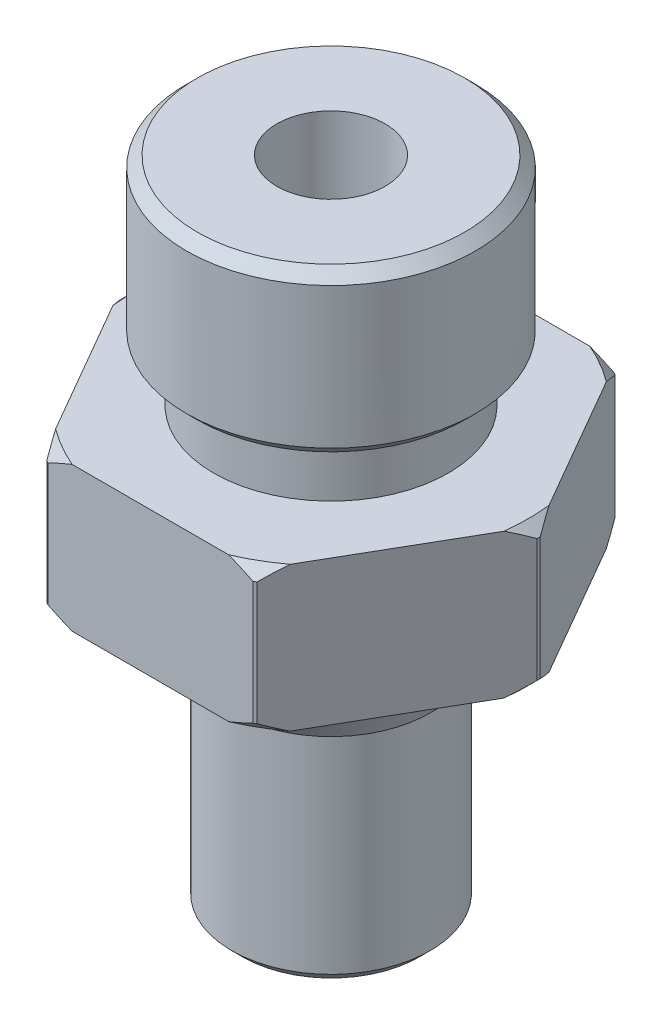
SolidWorks part; units mm, degrees
material "AISI 304"
ref_plane "Спереди" through (0, 0, 0) normal (0, 0, 1) x (1, 0, 0)
ref_plane "Сверху" through (0, 0, 0) normal (0, 1, 0) x (1, 0, 0)
ref_plane "Справа" through (0, 0, 0) normal (1, 0, 0) x (0, 0, -1)
ref_axis "ОсьX" through (-88.99, 0, 0) along (1, 0, 0)
ref_axis "ОсьZ" through (0, 55, 0) along (0, -1, 0)
ref_axis "ОсьY" through (0, 0, -88.99) along (0, 0, 1)
sketch "Эскиз1" plane through (0, 0, 0) normal (0, 0, 1) x (1, 0, 0)
  line L0 (0, 8.2669) -> (0, -10.3174) construction
  line L1 (1.5, 0) -> (4, 0)
  line L2 (4, 0) -> (4, -4.5)
  line L3 (4, -4.5) -> (3.25, -4.5)
  line L4 (3.25, -4.5) -> (3.25, -6)
  line L5 (3.25, -6) -> (5.75, -6)
  line L6 (5.75, -6) -> (5.75, -10)
  line L7 (5.75, -10) -> (3.6826, -10)
  line L8 (3.6826, -10) -> (2.75, -12)
  line L12 (1.5, 0) -> (1.5, -18)
  line L13 (2.75, -12) -> (2.75, -18)
  line L14 (2.75, -18) -> (1.5, -18)
  point P5 (2.5, -15.8304)
  dimension "D2" = 3
  dimension "D3" = 6
  dimension "D4" = 5.5
  dimension "D5" = 8
  dimension "D6" = 6.5
  dimension "D7" = 6
  dimension "D8" = 1.5
  dimension "D9" = 11.5
  dimension "D10" = 4
  dimension "D11" = 25
  dimension "D12" = 2
revolve "Повернуть1" add sketch "Эскиз1" angle 360 mid plane about L0
cosmetic thread "Условное изображение резьбы1" parameters "D2"=6.917
chamfer "Фаска1" distance 0.3 angle 45 6 edges at (0, -10, 5.75) (0, -6, 5.75) (0, -4.5, 4) (0, 0, 4) (0, -18, 1.5) (0, -18, 2.75)
sketch "Эскиз2" plane through (0, -6, 0) normal (0, 1, 0) x (1, 0, 0)
  line L1 (5.7735, 0) -> (2.8868, 5)
  line L2 (2.8868, 5) -> (-2.8868, 5)
  line L3 (-2.8868, 5) -> (-5.7735, 0)
  line L4 (-5.7735, 0) -> (-2.8868, -5)
  line L5 (-2.8868, -5) -> (2.8868, -5)
  line L6 (2.8868, -5) -> (5.7735, 0)
  circle A0 centre (0, 0) radius 5 construction
  dimension "D1" = 10
extrude "Вырез-Вытянуть1" cut sketch "Эскиз2" against normal through all flip side to cut
